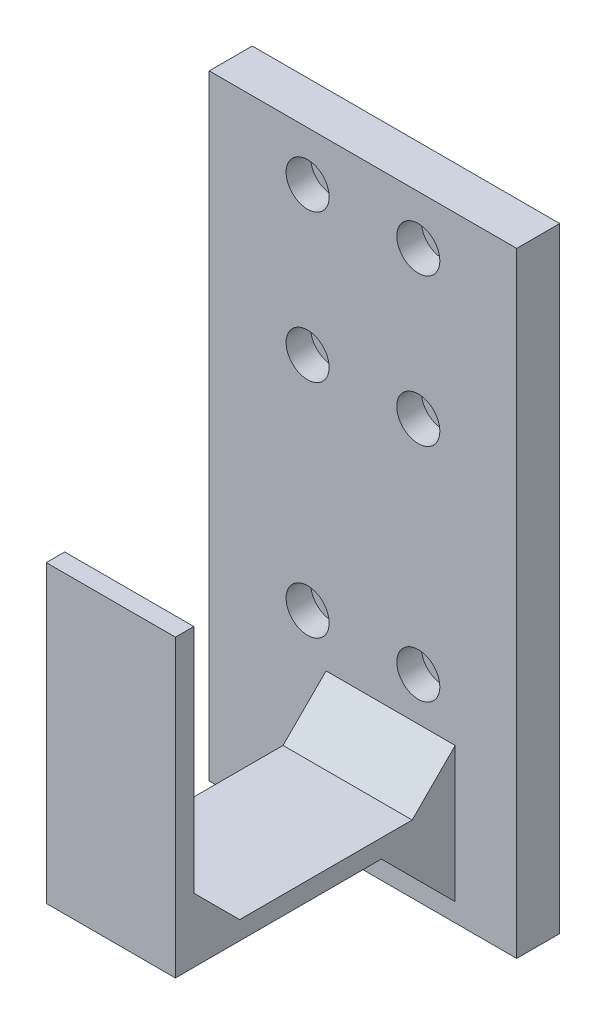
SolidWorks part; units mm, degrees
ref_plane "Front Plane" through (0, 0, 0) normal (0, 0, 1) x (1, 0, 0)
ref_plane "Top Plane" through (0, 0, 0) normal (0, 1, 0) x (1, 0, 0)
ref_plane "Right Plane" through (0, 0, 0) normal (1, 0, 0) x (0, 0, -1)
sketch "Sketch1" plane through (0, 0, 0) normal (0, 0, 1) x (1, 0, 0)
  line L1 (-25, -50) -> (25, -50)
  line L2 (-25, -50) -> (-25, 50)
  line L3 (-25, 50) -> (25, 50)
  line L4 (25, -50) -> (25, 50)
  line L5 (-25, -50) -> (25, 50) construction
  line L6 (-25, 50) -> (25, -50) construction
  point P0 (0, 0)
  dimension "D1" = 50
  dimension "D2" = 100
sketch "Sketch2" plane through (0, 0, 0) normal (0, 0, 1) x (1, 0, 0)
  line L0 (-9, 42) -> (9, 42) construction
  line L1 (9, 42) -> (9, 18) construction
  line L2 (9, 18) -> (-9, 18) construction
  line L3 (-9, 18) -> (-9, 42) construction
  line L4 (-9, 42) -> (9, 18) construction
  line L5 (9, 42) -> (-9, 18) construction
  line L6 (-9, -18) -> (9, -18) construction
  line L7 (9, -18) -> (9, -42) construction
  line L8 (9, -42) -> (-9, -42) construction
  line L9 (-9, -42) -> (-9, -18) construction
  line L10 (-9, -18) -> (9, -42) construction
  line L11 (9, -18) -> (-9, -42) construction
  line L12 (-9, 18) -> (-9, -18) construction
  line L13 (-9, -18) -> (9, 18) construction
  line L14 (9, 18) -> (9, -18) construction
  line L15 (9, -18) -> (-9, 18) construction
  circle A0 centre (-9, 42) radius 1.6
  circle A1 centre (9, 42) radius 1.6
  circle A2 centre (-9, 18) radius 1.6
  circle A3 centre (9, 18) radius 1.6
  circle A4 centre (9, -18) radius 1.6
  circle A5 centre (-9, -18) radius 1.6
  circle A6 centre (-9, -42) radius 1.6
  circle A7 centre (9, -42) radius 1.6
  point P2 (0, 0)
  point P5 (0, 0)
  dimension "D1" = 3.2
  dimension "D2" = 24
  dimension "D3" = 36
  dimension "D4" = 24
  dimension "D5" = 18
extrude "Boss-Extrude1" add sketch "Sketch1" against normal blind 7
extrude "Cut-Extrude1" cut sketch "Sketch2" against normal up to next
sketch "Sketch4" plane through (0, 0, 0) normal (0, 0, 1) x (1, 0, 0)
  line L0 (-25, -32) -> (25, -32) construction
  line L1 (-25, 50) -> (-25, -50) construction
  line L2 (25, -50) -> (25, 50) construction
  line L3 (-25, -35) -> (25, -35) construction
  line L4 (15, -32) -> (15, -35)
  line L5 (-6, -32) -> (-6, -35)
  line L6 (-6, -32) -> (15, -32)
  line L7 (15, -35) -> (-6, -35)
  dimension "D1" = 18
  dimension "D2" = 3
  dimension "D3" = 10
  dimension "D4" = 21
extrude "Boss-Extrude2" add sketch "Sketch4" along normal blind 45.5
sketch "Sketch5" plane through (0, -32, 0) normal (0, 1, 0) x (1, 0, 0)
  line L0 (15, -45.5) -> (15, 0) construction
  line L1 (-6, -45.5) -> (15, -45.5)
  line L2 (-6, -45.5) -> (-6, -35.1) construction
  line L3 (-6, -35.1) -> (15, -35.1) construction
  line L4 (15, -45.5) -> (15, -35.1) construction
  line L5 (-6, -42.5) -> (15, -42.5)
  line L6 (15, -42.5) -> (15, -45.5)
  line L7 (-6, -45.5) -> (-6, -42.5)
  dimension "D1" = 10.4
  dimension "D2" = 3
extrude "Boss-Extrude3" add sketch "Sketch5" along normal blind 45
ref_plane "Plane1" through (-6, 0, 0) normal (-1, 0, 0) x (0, 0, 1)
sketch "Sketch6" plane through (-6, 0, 0) normal (-1, 0, 0) x (0, 0, 1)
  line L0 (42.5, -24.55) -> (35.05, -32)
  line L1 (42.5, -32) -> (35.05, -32)
  line L2 (42.5, -32) -> (42.5, -24.55)
  line L3 (42.5, -24.55) -> (35.05, -24.55) construction
  line L4 (35.05, -32) -> (35.05, -24.55) construction
  dimension "D1" = 7.45
extrude "Boss-Extrude4" add sketch "Sketch6" against normal up to surface (21 mm away) up to face at (15, -18, 29.3333)
sketch "Sketch7" plane through (0, 0, 0) normal (0, 0, 1) x (1, 0, 0)
  line L0 (-6, -35) -> (15, -35) construction
  line L1 (15, -35) -> (-6, -35)
  line L2 (15, -35) -> (15, -47)
  line L3 (15, -47) -> (-6, -47)
  line L4 (-6, -35) -> (-6, -47)
  dimension "D1" = 12
sketch "Sketch8" plane through (0, -35, 0) normal (0, -1, 0) x (1, 0, 0)
  line L0 (15, 45.5) -> (15, 0) construction
  line L1 (-6, 0) -> (15, 0)
  line L2 (-6, 0) -> (-6, 12)
  line L3 (-6, 12) -> (15, 12)
  line L4 (15, 0) -> (15, 12)
  dimension "D1" = 12
loft "Loft1" add profiles "Sketch8", "Sketch7" connector at (-6, -35, 12) connector at (-6, -47, 0)
sketch "Sketch3" plane through (0, 0, 0) normal (0, 0, 1) x (1, 0, 0)
  line L0 (-9, 42) -> (9, 18) construction
  line L1 (9, 18) -> (9, 42) construction
  line L2 (9, 42) -> (-9, 18) construction
  line L3 (-9, 18) -> (-9, 42) construction
  line L4 (-9, 42) -> (9, 42) construction
  line L5 (-9, 18) -> (9, 18) construction
  line L6 (9, 18) -> (-9, -18) construction
  line L7 (-9, -18) -> (9, -18) construction
  line L8 (9, -18) -> (-9, 18) construction
  line L9 (-9, 18) -> (-9, -18) construction
  line L10 (-9, -18) -> (-9, -42) construction
  line L11 (-9, -42) -> (9, -42) construction
  line L12 (9, -42) -> (-9, -18) construction
  line L13 (9, 18) -> (9, -18) construction
  line L14 (9, -18) -> (9, -42) construction
  line L15 (9, -18) -> (-9, -42) construction
  circle A0 centre (-9, 42) radius 3.5
  circle A1 centre (9, 42) radius 3.5
  circle A2 centre (-9, 18) radius 3.5
  circle A3 centre (9, 18) radius 3.5
  circle A4 centre (-9, -18) radius 3.5
  circle A5 centre (9, -18) radius 3.5
  circle A6 centre (9, -42) radius 3.5
  circle A7 centre (-9, -42) radius 3.5
  point P24 (0, 0)
  point P25 (0, 0)
  dimension "D1" = 7
  dimension "D2" = 18
  dimension "D3" = 24
  dimension "D4" = 36
  dimension "D5" = 24
extrude "Cut-Extrude2" cut sketch "Sketch3" against normal blind 24 from offset 20
sketch "Sketch10" plane through (-6, 0, 0) normal (-1, 0, 0) x (0, 0, 1)
  line L0 (35.05, -32) -> (0, -32) construction
  line L1 (7, -32) -> (0, -32)
  line L2 (0, -32) -> (0, -25)
  line L3 (0, 50) -> (0, -50) construction
  line L4 (0, -25) -> (7, -32)
  dimension "D1" = 7
extrude "Boss-Extrude5" add sketch "Sketch10" against normal up to surface (21 mm away) up to face at (15, -22.6313, 30.725)
